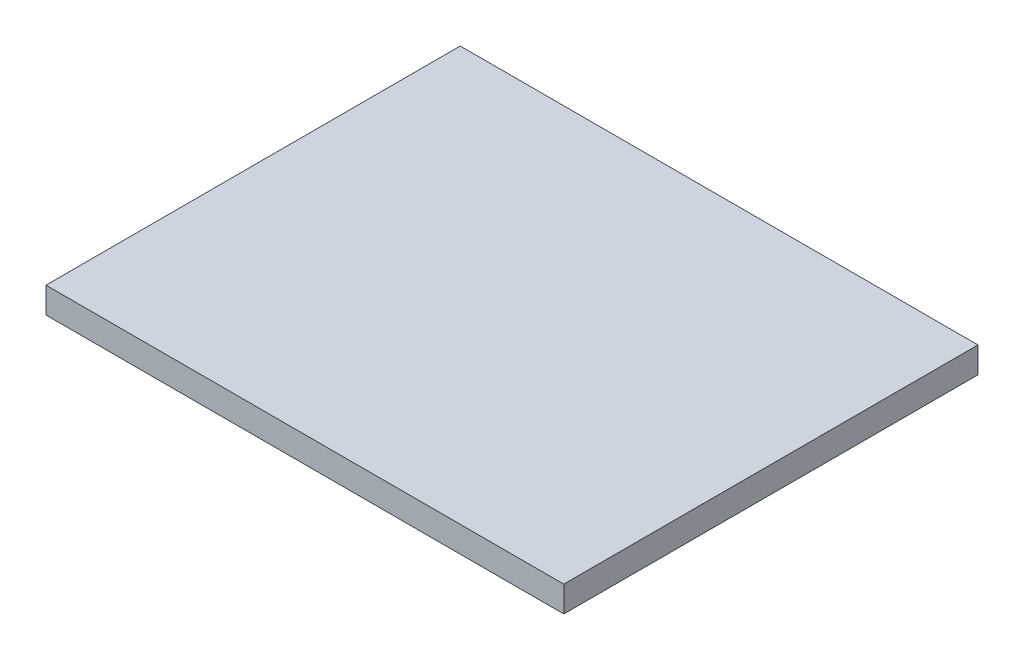
SolidWorks part; units mm, degrees
ref_plane "Front Plane" through (0, 0, 0) normal (0, 0, 1) x (1, 0, 0)
ref_plane "Top Plane" through (0, 0, 0) normal (0, 1, 0) x (1, 0, 0)
ref_plane "Right Plane" through (0, 0, 0) normal (1, 0, 0) x (0, 0, -1)
sketch "Sketch1" plane through (0, 0, 0) normal (0, 1, 0) x (1, 0, 0)
  line L1 (-63.5, 50.8) -> (63.5, 50.8)
  line L2 (-63.5, 50.8) -> (-63.5, -50.8)
  line L3 (-63.5, -50.8) -> (63.5, -50.8)
  line L4 (63.5, 50.8) -> (63.5, -50.8)
  line L5 (-63.5, 50.8) -> (63.5, -50.8) construction
  line L6 (-63.5, -50.8) -> (63.5, 50.8) construction
  line L7 (57.15, -44.45) -> (-57.15, -44.45)
  line L8 (57.15, -44.45) -> (57.15, 44.45)
  line L9 (57.15, 44.45) -> (-57.15, 44.45)
  line L10 (-57.15, -44.45) -> (-57.15, 44.45)
  line L11 (57.15, -44.45) -> (-57.15, 44.45) construction
  line L12 (57.15, 44.45) -> (-57.15, -44.45) construction
  point P0 (0, 0)
  point P6 (0, 0)
  dimension "D1" = 127
  dimension "D2" = 101.6
  dimension "D3" = 6.35
  dimension "D4" = 6.35
extrude "Boss-Extrude1" add sketch "Sketch1" along normal blind 6.35
extrude "Boss-Extrude2" add sketch "Sketch1<2>" along normal blind 6.35 contours L10 L7 L8 L9 region at (0, 0, 0)
sketch "Sketch1<2>" plane through (0, 0, 0) normal (0, 1, 0) x (1, 0, 0) same geometry as "Sketch1"
